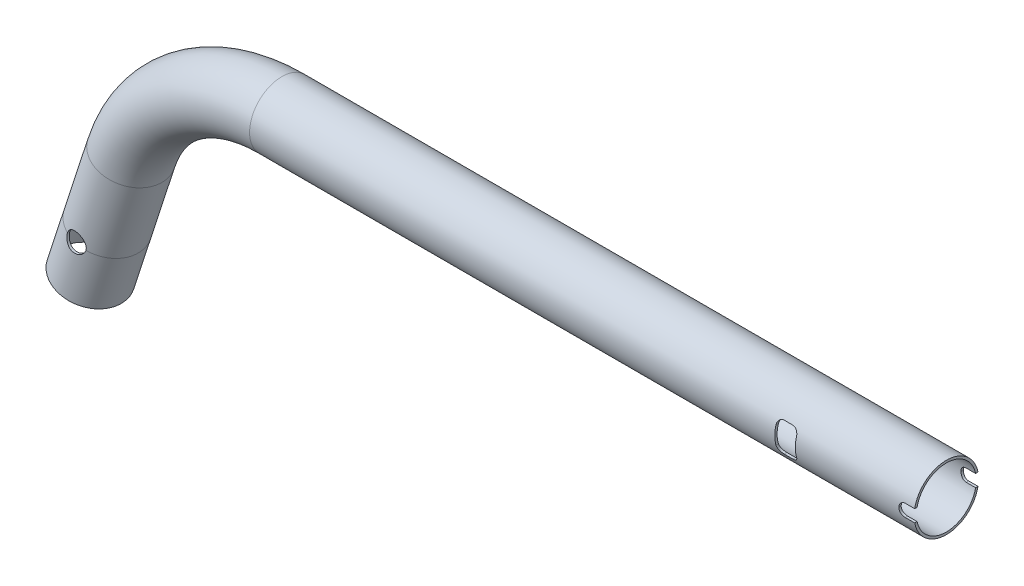
SolidWorks part; units mm, degrees
ref_plane "Front Plane" through (0, 0, 0) normal (0, 0, 1) x (1, 0, 0)
ref_plane "Top Plane" through (0, 0, 0) normal (0, 1, 0) x (1, 0, 0)
ref_plane "Right Plane" through (0, 0, 0) normal (1, 0, 0) x (0, 0, -1)
sketch "Sketch1" plane through (0, 0, 0) normal (0, 0, 1) x (1, 0, 0)
  line L0 (-91.2783, 0) -> (91.2783, 0)
  line L1 (-142.6354, -37.3131) -> (-150.7217, -62.2)
  line L2 (91.2783, 0) -> (135.2783, 0)
  line L3 (-150.7217, -62.2) -> (-156.5052, -80)
  arc A0 (-91.2783, 0) -> (-142.6354, -37.3131) centre (-91.2783, -54) ccw
  point P4 (0, 0)
  point P10 (-150.7217, -62.2)
  dimension "D2" = 54
  dimension "D1" = 72
  dimension "D3" = 62.2
  dimension "D4" = 242
  dimension "D5" = 80
  dimension "D6" = 72
  dimension "D7" = 44
ref_plane "Plane1" through (91.2783, 0, 0) normal (1, 0, 0) x (0, 0, -1)
sketch "Sketch3" plane through (91.2783, 0, 0) normal (1, 0, 0) x (0, 0, -1)
  circle A0 centre (0, 0) radius 11
  circle A1 centre (0, 0) radius 10.2
  dimension "D1" = 0.8
  dimension "D2" = 22
sweep "Sweep2" add profiles "Sketch3" path "Sketch1"
ref_axis "Axis1" through (135.2783, 0, 0) along (-1, 0, 0)
ref_axis "Axis2" through (-140.6374, -31.1639, 0) along (-0.309, -0.9511, 0)
sketch "Sketch4" plane through (0, 0, 0) normal (0, 0, 1) x (1, 0, 0)
  line L0 (-161.1833, -58.8008) -> (-140.26, -65.5992) construction
  line L1 (91.2783, -101.4635) -> (91.2783, 101.4635) construction
  line L2 (135.2783, 0) -> (91.2783, 0) construction
  line L3 (135.2783, -11) -> (135.2783, 11) construction
  line L4 (135.2783, 0) -> (-91.2783, 0) construction
  line L5 (135.282, 2.1) -> (135.282, -2.1)
  line L6 (89.7783, -5) -> (92.7783, -5)
  line L7 (87.7783, -3) -> (87.7783, 3)
  line L8 (89.7783, 5) -> (92.7783, 5)
  line L9 (94.7783, -3) -> (94.7783, 3)
  line L10 (87.7783, -5) -> (94.7783, 5) construction
  line L11 (87.7783, 5) -> (94.7783, -5) construction
  line L12 (132.082, -2.1) -> (135.282, -2.1)
  line L13 (130.082, -0.1) -> (130.082, 0.1)
  line L14 (132.082, 2.1) -> (135.282, 2.1)
  line L16 (130.082, -2.1) -> (135.2783, 0) construction
  line L17 (130.082, 2.1) -> (135.2783, 0) construction
  circle A0 centre (-150.7217, -62.2) radius 3.3
  arc A1 (89.7783, -5) -> (87.7783, -3) centre (89.7783, -3) cw
  arc A2 (94.7783, -3) -> (92.7783, -5) centre (92.7783, -3) cw
  arc A3 (92.7783, 5) -> (94.7783, 3) centre (92.7783, 3) cw
  arc A4 (89.7783, 5) -> (87.7783, 3) centre (89.7783, 3) ccw
  arc A5 (132.082, -2.1) -> (130.082, -0.1) centre (132.082, -0.1) cw
  arc A6 (130.082, 0.1) -> (132.082, 2.1) centre (132.082, 0.1) cw
  point P38 (135.282, 0)
  dimension "D1" = 44
  dimension "D4" = 2
  dimension "D5" = 2
  dimension "D6" = 6.6
  dimension "D2" = 7
  dimension "D3" = 10
  dimension "D7" = 4.2
extrude "Cut-Extrude1" cut sketch "Sketch4" along normal up to next
sketch "Sketch5" plane through (0, 0, 0) normal (0, 0, 1) x (1, 0, 0)
  line L0 (-160.4224, -59.048) -> (-141.0209, -65.352) construction
  circle A0 centre (-150.7217, -62.2) radius 3.3
extrude "Cut-Extrude2" cut sketch "Sketch5" against normal through all
sketch "Sketch6" plane through (0, 0, 0) normal (0, 0, 1) x (1, 0, 0)
  line L2 (130.082, 0.1) -> (130.082, -0.1)
  line L3 (132.082, -2.1) -> (135.2783, -2.1)
  line L4 (135.2783, -2.1) -> (135.2783, 2.1)
  line L5 (135.2783, 2.1) -> (132.082, 2.1)
  arc A0 (132.082, -2.1) -> (130.082, -0.1) centre (132.082, -0.1) cw
  arc A1 (130.082, 0.1) -> (132.082, 2.1) centre (132.082, 0.1) cw
  dimension "D1" = 2
extrude "Cut-Extrude3" cut sketch "Sketch6" against normal through all and the other way through all
